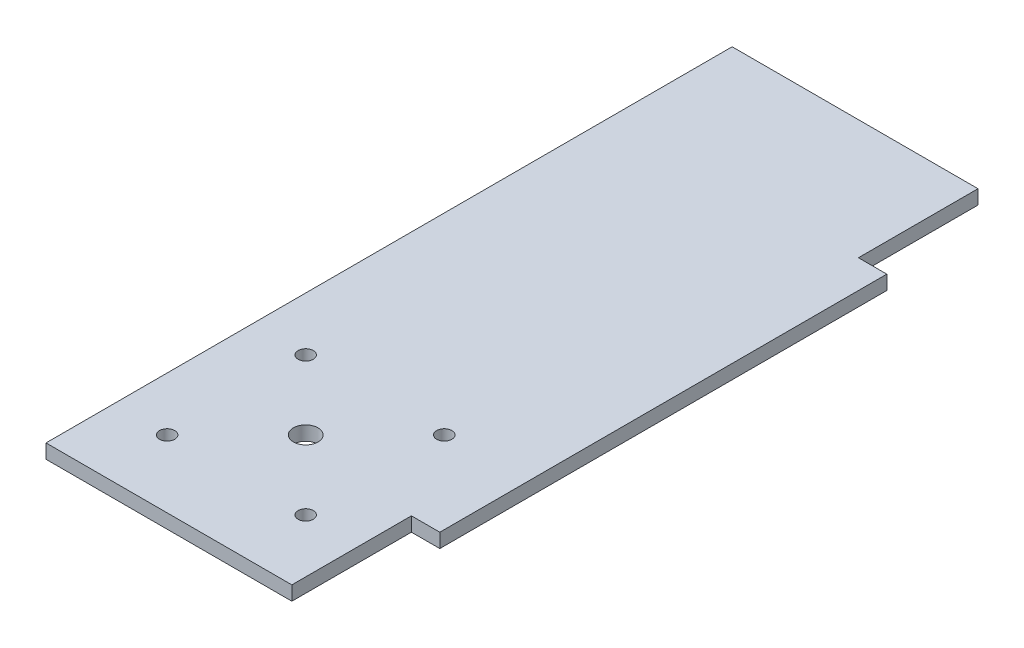
SolidWorks part; units mm, degrees
material "Cedar"
ref_plane "Front Plane" through (0, 0, 0) normal (0, 0, 1) x (1, 0, 0)
ref_plane "Top Plane" through (0, 0, 0) normal (0, 1, 0) x (1, 0, 0)
ref_plane "Right Plane" through (0, 0, 0) normal (1, 0, 0) x (0, 0, -1)
sketch "Sketch1" plane through (0, 0, 0) normal (0, 1, 0) x (1, 0, 0)
  line L0 (-27.5, 26.75) -> (27.5, 26.75)
  line L1 (27.5, 26.75) -> (27.5, 0)
  line L2 (27.5, 0) -> (33.85, 0)
  line L3 (33.85, 0) -> (33.85, -100)
  line L4 (33.85, -100) -> (27.5, -100)
  line L5 (27.5, -100) -> (27.5, -126.75)
  line L6 (27.5, -126.75) -> (-27.5, -126.75)
  line L7 (-27.5, -126.75) -> (-27.5, -100)
  line L8 (-27.5, -100) -> (-33.85, -100)
  line L9 (-33.85, -100) -> (-33.85, 0)
  line L10 (-33.85, 0) -> (-27.5, 0)
  line L11 (-27.5, 0) -> (-27.5, 26.75)
  line L12 (-27.5, 0) -> (-27.5, -100) construction
  point P11 (0, 26.75)
  point P14 (-33.85, -50)
  dimension "D1" = 6.35
  dimension "D2" = 100
  dimension "D3" = 55
  dimension "D4" = 153.5
extrude "Boss-Extrude1" add sketch "Sketch1" along normal blind 3.175 contours L11 L12 L7 L6 L5 L4 L3 L2 L1 L0 region at (2.1458, 0, 50)
sketch "Sketch3" plane through (0, 3.175, 0) normal (0, 1, 0) x (1, 0, 0)
  line L0 (-27.5, 26.75) -> (27.5, 26.75) construction
  line L1 (21.25, -117.4) -> (-21.25, -117.4) construction
  line L2 (21.25, -117.4) -> (21.25, -74.9) construction
  line L3 (21.25, -74.9) -> (-21.25, -74.9) construction
  line L4 (-21.25, -117.4) -> (-21.25, -74.9) construction
  line L5 (21.25, -117.4) -> (-21.25, -74.9) construction
  line L6 (21.25, -74.9) -> (-21.25, -117.4) construction
  line L7 (0, -71.65) -> (0, -120.65) construction
  circle A0 centre (0, -96.15) radius 2.75
  point P0 (0, -96.15)
  point P5 (0, -81.25)
  point P13 (15.5, -111.65)
  point P14 (-15.5, -111.65)
  point P15 (-15.5, -80.65)
  point P16 (15.5, -80.65)
  dimension "D4" = 5.5
  dimension "D1" = 108
  dimension "D2" = 6.35
  dimension "D5" = 49
  dimension "D3" = 42.5
  dimension "D6" = 31
extrude "Cut-Extrude1" cut sketch "Sketch3" against normal through all
hole_wizard "M3 Clearance Hole1" positions "Sketch5" profile "Sketch4" hole size "M3" standard "ANSI Metric" end condition through all
sketch "Sketch5" plane through (0, 3.175, 0) normal (0, 1, 0) x (1, 0, 0)
  point P6 (15.5, -111.65)
  point P9 (-15.5, -111.65)
  point P12 (-15.5, -80.65)
  point P15 (15.5, -80.65)
sketch "Sketch4" plane through (15.5, 3.175, 111.65) normal (1, 0, 0) x (0, 0, 1)
  line L0 (0, 0) -> (0, 3.175)
  line L1 (0, 3.175) -> (1.7, 3.175)
  line L2 (1.7, 3.175) -> (1.7, 0)
  line L5 (1.7, 0) -> (0, 0)
  line L11 (0, -6.35) -> (0, 107.95) construction
  dimension "Thru Hole Dia." = 3.4
  dimension "Thru Hole Depth" = 3.175
equation "\"length\"= 153.5mm"
equation "\"w_mach\" = 55mm"
equation "\"w_tab\"= 100mm"
equation "\"t_wood\"= 0.125in"
equation "\"t_side\"= 0.25in"
equation "\"D1@Sketch1\"=\"t_side\""
equation "\"D2@Sketch1\"=\"w_tab\""
equation "\"D3@Sketch1\"=\"w_mach\""
equation "\"D4@Sketch1\"=\"length\""
equation "\"D1@Boss-Extrude1\"=\"t_wood\""
equation "\"l_motor\"= 42.5mm"
equation "\"l_servo\" = 0"
equation "\"servocenter\"= 6.35mm"
equation "\"servoholes\"= 49mm"
equation "\"dY\"= 124mm"
equation "\"in_rad\"= 16mm"
equation "\"D1@Sketch3\"= \"dY\" - \"in_rad\""
equation "\"D2@Sketch3\"=\"servocenter\""
equation "\"D5@Sketch3\"=\"servoholes\""
equation "\"D3@Sketch3\"=\"l_motor\""
